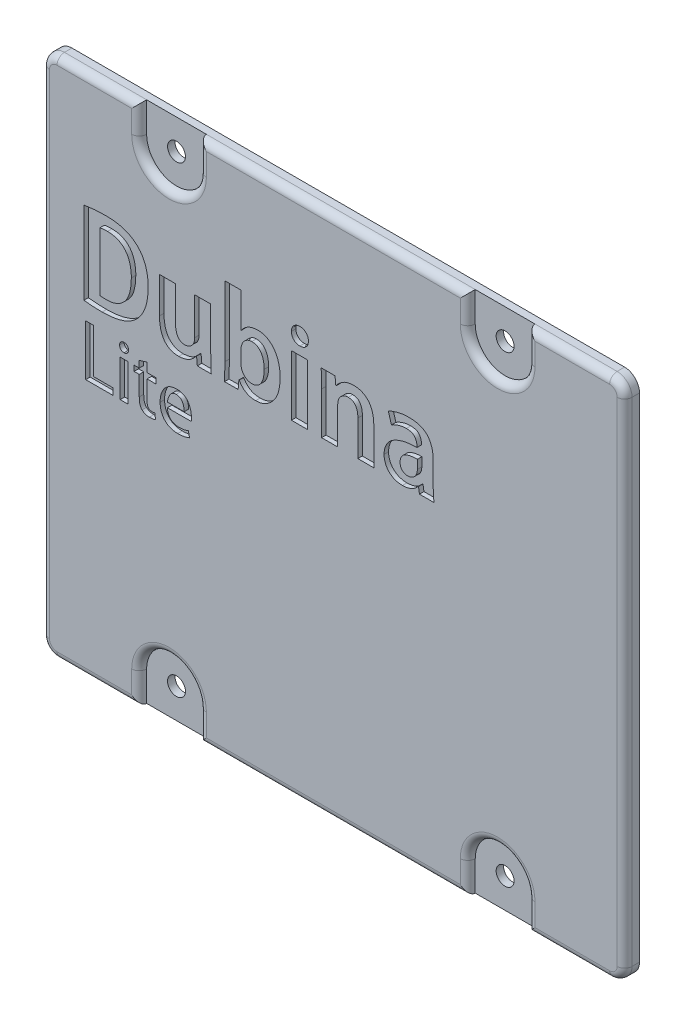
SolidWorks part; units mm, degrees
ref_plane "Спереди" through (0, 0, 0) normal (0, 0, 1) x (1, 0, 0)
ref_plane "Сверху" through (0, 0, 0) normal (0, 1, 0) x (1, 0, 0)
ref_plane "Справа" through (0, 0, 0) normal (1, 0, 0) x (0, 0, -1)
other "Configuration Table"
sketch "Эскиз2" plane through (0, 0, 0) normal (0, 0, 1) x (1, 0, 0)
  line L0 (-37, 35) -> (37, 35)
  line L1 (39, 33) -> (39, -33)
  line L2 (37, -35) -> (-37, -35)
  line L3 (-39, -33) -> (-39, 33)
  line L4 (-18, -31) -> (-18, -35)
  line L5 (-26, -31) -> (-26, -35)
  line L6 (26, -31) -> (26, -35)
  line L7 (18, -31) -> (18, -35)
  line L8 (26, 31) -> (26, 35)
  line L9 (18, 31) -> (18, 35)
  line L10 (-18, 31) -> (-18, 35)
  line L11 (-26, 31) -> (-26, 35)
  line L12 (0, 0) -> (0, 47.6703) construction
  line L13 (0, 0) -> (66.8119, 0) construction
  arc A0 (-39, -33) -> (-37, -35) centre (-37, -33) ccw
  arc A1 (37, -35) -> (39, -33) centre (37, -33) ccw
  arc A2 (37, 35) -> (39, 33) centre (37, 33) cw
  arc A3 (-39, 33) -> (-37, 35) centre (-37, 33) cw
  circle A12 centre (-22, 31) radius 1.2
  circle A13 centre (22, 31) radius 1.2
  circle A14 centre (22, -31) radius 1.2
  circle A15 centre (-22, -31) radius 1.2
  arc A16 (-26, 31) -> (-18, 31) centre (-22, 31) ccw
  arc A17 (18, 31) -> (26, 31) centre (22, 31) ccw
  arc A18 (26, -31) -> (18, -31) centre (22, -31) ccw
  arc A19 (-18, -31) -> (-26, -31) centre (-22, -31) ccw
  point P0 (0, 0)
  point P19 (0, 35)
  point P24 (0, 0)
  point P25 (0, 0)
  point P26 (0, 0)
  point P27 (0, 0)
  circle M9 centre (-22, -31) radius 1.2
  line M10 (-41, -29) -> (-41, -33)
  arc M11 (-41, -33) -> (-39, -35) centre (-39, -33) ccw
  line M12 (-39, -35) -> (-15, -35)
  line M13 (-15, -35) -> (-15, -29)
  line M14 (-15, -29) -> (-10, -20.5)
  line M15 (-10, -20.5) -> (-29, -20.5)
  line M17 (-29, -29) -> (-41, -29)
  dimension "D3" = 2
  dimension "D4" = 44
  dimension "D6" = 2.4
  dimension "D1" = 70
  dimension "D2" = 78
  dimension "D5" = 62
extrude "Бобышка-Вытянуть1" add sketch "Эскиз2" along normal blind 2 contours A18 L6 L2 L1 L0 L8 A17 L9 L10 A16 L11 L3 L7 M17 M15 M14 M13 | A19 L4 L2 L5 M13 M14 M15 M17 M10 M11 M12 region at (0, 0, 0)
extrude "Бобышка-Вытянуть2" add sketch "Эскиз2<3>" along normal blind 1 contours L4 A19 L5 L2 M9 | L6 A18 L7 L2 A14 | L9 A17 L8 L0 A13 | L11 A16 L10 L0 A12 region at (-22, 34.8869, 0) region at (22, 34.8869, 0) region at (-25.8869, -33, 0) region at (18.1131, -33, 0)
sketch "Эскиз2<3>" plane through (0, 0, 0) normal (0, 0, 1) x (1, 0, 0) same geometry as "Эскиз2"
fillet "Скругление1" radius 1 24 edges at (-31.5, 35, 2) (-26, 33, 2) (-22, 27, 2) (-18, 33, 2) (0, 35, 2) (18, 33, 2) (22, 27, 2) (26, 33, 2) (31.5, 35, 2) (39, 0, 2) (31.5, -35, 2) (26, -33, 2) (22, -27, 2) (18, -33, 2) (0, -35, 2) (-18, -33, 2) (-22, -27, 2) (-26, -33, 2) (-31.5, -35, 2) (-38.4142, 34.4142, 2) (38.4142, 34.4142, 2) (38.4142, -34.4142, 2) (-38.4142, -34.4142, 2) (-39, 0, 2)
sketch "Эскиз3" plane through (0, 0, 2) normal (0, 0, 1) x (1, 0, 0)
  text T0 "Dubina" font "Adobe Gothic Std B" height in points 36
  text T1 "Lite" font "Adobe Heiti Std R" height in points 22
extrude "Вырез-Вытянуть1" cut sketch "Эскиз3" against normal blind 0.6
